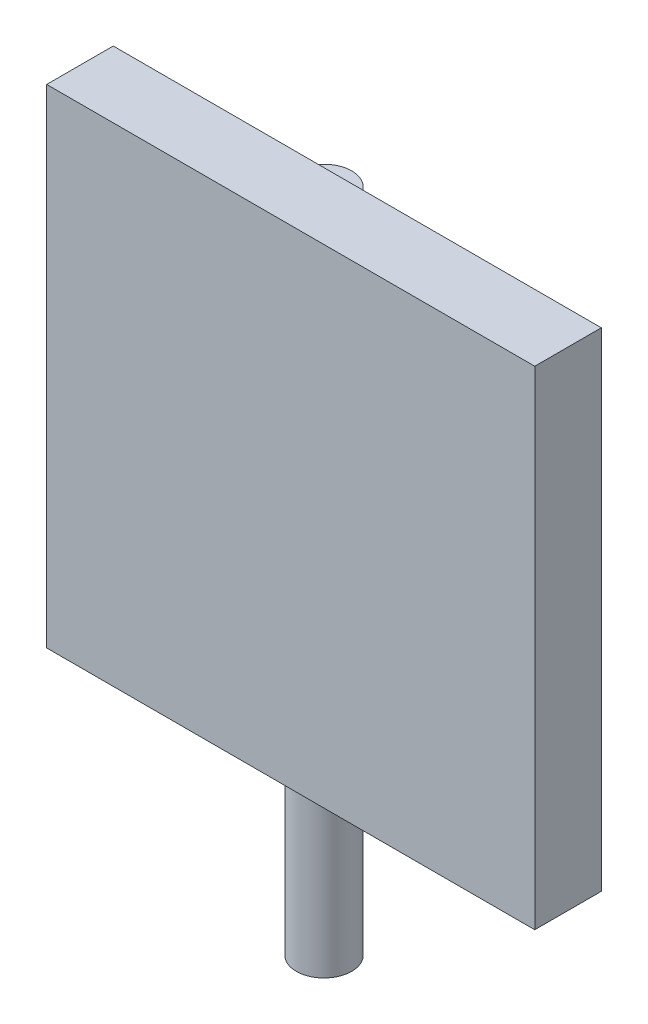
SolidWorks part; units mm, degrees
material "3.0517 (EN-AW 3003)"
ref_plane "Front" through (0, 0, 0) normal (0, 0, 1) x (1, 0, 0)
ref_plane "Top" through (0, 0, 0) normal (0, 1, 0) x (1, 0, 0)
ref_plane "Right" through (0, 0, 0) normal (1, 0, 0) x (0, 0, -1)
sketch "Sketch1" plane through (0, 0, 0) normal (0, 0, 1) x (1, 0, 0)
  line L1 (-2, 4) -> (2, 4)
  line L2 (-2, 4) -> (-2, 0)
  line L3 (-2, 0) -> (2, 0)
  line L4 (2, 4) -> (2, 0)
  dimension "D1" = 4
  dimension "D2" = 4
extrude "Boss-Extrude1" add sketch "Sketch1" along normal mid plane 0.2
sketch "Sketch2" plane through (0, 0, 0) normal (0, 1, 0) x (1, 0, 0)
  line L0 (-2, 0.1) -> (2, 0.1) construction
  line L1 (-2, 0.1) -> (2, 0.1) construction
  line L2 (-0.1, 0.35) -> (0, 0) construction
  circle A0 centre (-0.35, 0.35) radius 0.25
  dimension "D1" = 0.5
  dimension "D2" = 0.1
extrude "Boss-Extrude2" add sketch "Sketch2" along normal up to surface (4 mm away) and the other way blind 2 separate body up to face at (0, 4, 0)
sketch "Sketch3" plane through (0, 0, -0.1) normal (0, 0, -1) x (-1, 0, 0)
  line L0 (-2, 4) -> (2, 4) construction
  line L1 (0.6, 4) -> (0.1, 4) construction
  line L2 (0.6, 4) -> (0.1, 4) construction
  line L3 (0.475, 4) -> (0.475, 3) construction
  circle A0 centre (0.725, 3) radius 0.25
  dimension "D1" = 0.5
  dimension "D2" = 1
  dimension "D3" = 0.125
extrude "Boss-Extrude3" add sketch "Sketch3" along normal blind 0.5 draft 3
sketch "Sketch4" plane through (0, 0, 0) normal (0, 0, 1) x (1, 0, 0)
  line L8 (-2.2, 4.2) -> (-2.2, -0.2)
  line L9 (-2.2, -0.2) -> (2.2, -0.2)
  line L10 (2.2, -0.2) -> (2.2, 4.2)
  line L11 (2.2, 4.2) -> (-2.2, 4.2)
  line L12 (-2.2, 4.2) -> (-2.2, -0.2)
  line L13 (-2.2, -0.2) -> (2.2, -0.2)
  line L14 (2.2, -0.2) -> (2.2, 4.2)
  line L15 (2.2, 4.2) -> (-2.2, 4.2)
  dimension "D1" = 0.2
extrude "Boss-Extrude4" add sketch "Sketch4" along normal mid plane 0.6
